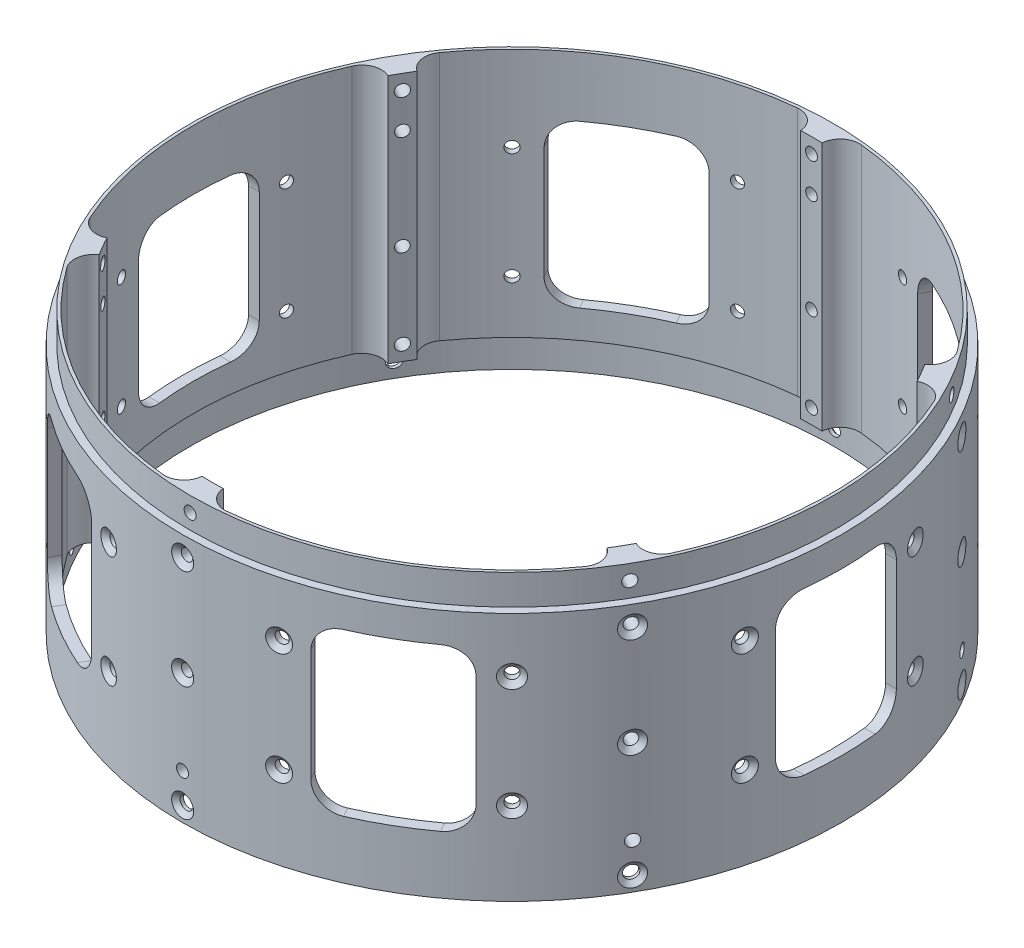
SolidWorks part; units mm, degrees
material "6061-T6 (SS)"
ref_plane "Front Plane" through (0, 0, 0) normal (0, 0, 1) x (1, 0, 0)
ref_plane "Top Plane" through (0, 0, 0) normal (0, 1, 0) x (1, 0, 0)
ref_plane "Right Plane" through (0, 0, 0) normal (1, 0, 0) x (0, 0, -1)
sketch "Sketch1" plane through (0, 0, 0) normal (0, 0, 1) x (1, 0, 0)
  line L0 (0, 42.3951) -> (0, -32.8937) construction
  line L1 (0, -35.6235) -> (0, 35.6235) construction
  line L2 (76.2, -63.5) -> (76.2, 0)
  line L3 (76.2, 0) -> (81.8896, 0)
  line L4 (81.8896, 0) -> (81.8896, -7.6708)
  line L5 (81.8896, -7.6708) -> (83.82, -7.6708)
  line L6 (83.82, -7.6708) -> (83.82, -71.12)
  line L7 (83.82, -71.12) -> (81.9404, -71.12)
  line L8 (81.9404, -71.12) -> (81.9404, -63.5)
  line L9 (81.9404, -63.5) -> (76.2, -63.5)
  line L10 (81.8896, -7.62) -> (84.2911, -7.62) construction
  dimension "D5" = 5.6896
  dimension "D10" = 76.2
  dimension "D2" = 7.62
  dimension "D4" = 7.62
  dimension "D6" = 7.62
revolve "Revolve1" add sketch "Sketch1" angle 360 about L0
sketch "Sketch2" plane through (0, 0, 0) normal (0, 1, 0) x (1, 0, 0)
  line L0 (0, 0) -> (0, 112.6688) construction
  line L1 (0, -35.6235) -> (0, 35.6235) construction
  line L2 (0, 0) -> (-128.6689, 74.287) construction
  line L3 (0, 0) -> (-50.2561, 87.0461) construction
  line L4 (0, 0) -> (-7.6343, 75.8166) construction
  arc A0 (-7.6343, 75.8166) -> (-61.8419, 44.5198) centre (0, 0) ccw construction
  arc A1 (-8.128, 80.7194) -> (-65.841, 47.3988) centre (0, 0) ccw
  arc A2 (-7.1406, 70.9138) -> (-57.8428, 41.6409) centre (0, 0) ccw
  arc A3 (-7.1406, 70.9138) -> (-8.128, 80.7194) centre (-7.6343, 75.8166) ccw
  arc A4 (-65.841, 47.3988) -> (-57.8428, 41.6409) centre (-61.8419, 44.5198) ccw
  circle A5 centre (0, 0) radius 81.8896 construction
  circle A7 centre (0, 0) radius 76.2 construction
  point P5 (-38.1, 65.9911)
  dimension "D2" = 0.762
  dimension "D1" = 60
  dimension "D3" = 30
  dimension "D4" = 5.75
extrude "Cut-Extrude1" cut sketch "Sketch2" against normal through all
pattern_circular "CirPattern1" count 6 over 360 about axis through (0, 42.3951, 0) along (0, 1, 0) of "Cut-Extrude1"
ref_plane "Plane1" through (0, 0, 83.82) normal (0, 0, 1) x (1, 0, 0)
hole_wizard "Tapped Hole for #4-40 Helicoil1" positions "Sketch3" profile "Sketch4" tap size "#4-40" standard "Helicoil® Inch"
sketch "Sketch3" plane through (0, 0, 83.82) normal (0, 0, 1) x (1, 0, 0)
  line L0 (81.8896, 0) -> (-81.8896, 0) construction
  line L1 (2.7181, 0) -> (-2.7181, 0) construction
  line L2 (2.7181, 0) -> (-2.7181, 0) construction
  line L3 (0, 0) -> (0, -3.81) construction
  line L5 (-2.7181, -63.5) -> (2.7181, -63.5) construction
  line L6 (-2.7181, -63.5) -> (2.7181, -63.5) construction
  line L7 (0, -63.5) -> (0, -59.69) construction
  point P0 (0, -3.81)
  point P20 (0, -59.69)
  point P41 (0, 0)
  point P42 (0, 0)
  dimension "D1" = 3.81
  dimension "D2" = 3.81
cosmetic thread "Hole Thread1" parameters "D1"=3.556, "D2"=3.7414
cosmetic thread "Hole Thread6" parameters "D1"=3.556, "D2"=3.7414
sketch "Sketch4" plane through (0, -3.81, 83.82) normal (1, 0, 0) x (0, -1, 0)
  line L0 (0, 0) -> (0, 26.3157)
  line L1 (0, 26.3157) -> (1.524, 25.4)
  line L2 (1.524, 25.4) -> (1.524, 0)
  line L5 (1.524, 0) -> (0, 0)
  line L10 (0, 26.3157) -> (-1.524, 25.4) construction
  line L11 (0, -6.35) -> (0, 107.95) construction
  dimension "Tap Drill Dia." = 3.048
  dimension "Tap Drill Depth" = 25.4
  dimension "Drill Angle" = 118
hole_wizard "CSK for #4 Flat Head Machine Screw (100)1" positions "Sketch5" profile "Sketch6" countersink size "#4" standard "ANSI Inch"
sketch "Sketch5" plane through (0, 0, 83.82) normal (0, 0, 1) x (1, 0, 0)
  line L0 (-2.7181, -63.5) -> (2.7181, -63.5) construction
  line L1 (-2.7181, -63.5) -> (2.7181, -63.5) construction
  line L2 (0, -63.5) -> (0, -67.31) construction
  point P0 (0, -67.31)
  dimension "D1" = 3.81
sketch "Sketch6" plane through (0, -67.31, 83.82) normal (1, 0, 0) x (0, -1, 0)
  line L0 (0, 0) -> (0, 26.3806)
  line L1 (0, 26.3806) -> (1.6319, 25.4)
  line L2 (1.6319, 25.4) -> (1.6319, 1.0284)
  line L3 (1.6319, 1.0284) -> (2.8575, 0)
  line L5 (2.8575, 0) -> (0, 0)
  line L6 (-1.6319, 1.0284) -> (-2.8575, 0) construction
  line L10 (0, 26.3806) -> (-1.632, 25.4) construction
  line L11 (0, -6.35) -> (0, 107.95) construction
  dimension "Hole Dia." = 3.2639
  dimension "Hole Depth" = 25.4
  dimension "Near C'Sink Dia." = 5.715
  dimension "Near C'Sink Angle" = 100
  dimension "Drill Angle" = 118
hole_wizard "CSK for #4 Flat Head Machine Screw (100)3" positions "Sketch12" profile "Sketch13" countersink size "#4" standard "ANSI Inch"
sketch "Sketch12" plane through (0, 0, 83.82) normal (0, 0, 1) x (1, 0, 0)
  line L0 (-2.7181, -63.5) -> (2.7181, -63.5) construction
  point P0 (0, -38.1)
  point P2 (0, -12.7)
  point P6 (0, -63.5)
  dimension "D1" = 25.4
  dimension "D2" = 50.8
sketch "Sketch13" plane through (0, -38.1, 83.82) normal (1, 0, 0) x (0, -1, 0)
  line L0 (0, 0) -> (0, 26.2852)
  line L1 (0, 26.2852) -> (1.4732, 25.4)
  line L2 (1.4732, 25.4) -> (1.4732, 1.1616)
  line L3 (1.4732, 1.1616) -> (2.8575, 0)
  line L5 (2.8575, 0) -> (0, 0)
  line L6 (-1.4732, 1.1616) -> (-2.8575, 0) construction
  line L10 (0, 26.2852) -> (-1.4732, 25.4) construction
  line L11 (0, -6.35) -> (0, 107.95) construction
  dimension "Hole Dia." = 2.9464
  dimension "Hole Depth" = 25.4
  dimension "Near C'Sink Dia." = 5.715
  dimension "Near C'Sink Angle" = 100
  dimension "Drill Angle" = 118
pattern_circular "CirPattern2" count 6 over 360 about axis through (0, 42.3951, 0) along (0, 1, 0) of "Tapped Hole for #4-40 Helicoil1", "CSK for #4 Flat Head Machine Screw (100)1", "CSK for #4 Flat Head Machine Screw (100)3"
sketch "Sketch7" plane through (0, 0, 0) normal (1, 0, 0) x (0, 0, -1)
  line L1 (-9.017, -15.24) -> (9.017, -15.24)
  line L2 (-15.367, -21.59) -> (-15.367, -50.038)
  line L3 (-9.017, -56.388) -> (9.017, -56.388)
  line L4 (15.367, -21.59) -> (15.367, -50.038)
  line L5 (-15.367, -15.24) -> (15.367, -56.388) construction
  line L6 (-15.367, -56.388) -> (15.367, -15.24) construction
  arc A0 (-15.367, -50.038) -> (-9.017, -56.388) centre (-9.017, -50.038) ccw
  arc A1 (9.017, -56.388) -> (15.367, -50.038) centre (9.017, -50.038) ccw
  arc A2 (15.367, -21.59) -> (9.017, -15.24) centre (9.017, -21.59) ccw
  arc A3 (-9.017, -15.24) -> (-15.367, -21.59) centre (-9.017, -21.59) ccw
  point P0 (0, -35.814)
  dimension "D4" = 6.35
  dimension "D1" = 41.148
  dimension "D2" = 30.734
  dimension "D3" = 15.24
extrude "Cut-Extrude2" cut sketch "Sketch7" against normal through all
sketch "Sketch9" plane through (0, -7.6708, 0) normal (0, 1, 0) x (1, 0, 0)
  line L0 (-49.5, 0) -> (-83.82, 0)
  line L1 (-50.2347, -13.4603) -> (-80.9639, -21.6942)
  line L2 (-83.82, 11.0351) -> (-83.82, -11.0351) construction
  line L3 (-83.82, -11.0351) -> (-78.1078, -32.3533) construction
  arc A0 (-83.3336, 9.017) -> (-83.3336, -9.017) centre (0, 0) ccw construction
  circle A1 centre (0, 0) radius 83.82 construction
  dimension "D1" = 15
ref_plane "Plane3" through (-80.9639, -7.6708, 21.6942) normal (-0.9659, 0, 0.2588) x (0.2588, 0, 0.9659)
hole_wizard "CSK for #4 Flat Head Machine Screw (100)2" positions "Sketch10" profile "Sketch11" countersink size "#4" standard "ANSI Inch"
sketch "Sketch10" plane through (-80.9639, -7.6708, 21.6942) normal (-0.9659, 0, 0.2588) x (0.2588, 0, 0.9659)
  line L0 (0, 0) -> (0, -13.9192) construction
  line L1 (0, -13.9192) -> (0, -42.3672) construction
  line L3 (0, -13.9192) -> (-6.4831, -13.9192) construction
  line L5 (0, -28.1432) -> (-6.4831, -28.1432) construction
  line L8 (-6.4831, -13.9192) -> (-6.4831, -42.3672) construction
  point P0 (0, -13.9192)
  point P2 (0, -42.3672)
  point P19 (0, 0)
  point P23 (0, 0)
sketch "Sketch11" plane through (-80.9639, -21.59, 21.6942) normal (0, 1, 0) x (0.2588, 0, 0.9659)
  line L0 (0, 0) -> (0, 26.2852)
  line L1 (0, 26.2852) -> (1.4732, 25.4)
  line L2 (1.4732, 25.4) -> (1.4732, 1.1616)
  line L3 (1.4732, 1.1616) -> (2.8575, 0)
  line L5 (2.8575, 0) -> (0, 0)
  line L6 (-1.4732, 1.1616) -> (-2.8575, 0) construction
  line L10 (0, 26.2852) -> (-1.4732, 25.4) construction
  line L11 (0, -6.35) -> (0, 107.95) construction
  dimension "Hole Dia." = 2.9464
  dimension "Hole Depth" = 25.4
  dimension "Near C'Sink Dia." = 5.715
  dimension "Near C'Sink Angle" = 100
  dimension "Drill Angle" = 118
mirror "Mirror1" about plane through (0, 0, 0) normal (0, 0, 1) of "CSK for #4 Flat Head Machine Screw (100)2"
pattern_circular "CirPattern5" count 6 over 360 about axis through (0, -7.6708, 0) along (0, 1, 0) of "Cut-Extrude2", "Mirror1"
ref_plane "Plane2" [suppressed] through (0, 0, 0) normal (-0.7071, 0, 0.7071) x (0.7071, 0, 0.7071)
sketch "Sketch8" [suppressed] plane through (0, 0, 0) normal (-0.7071, 0, 0.7071) x (0.7071, 0, 0.7071)
  line L0 (0, 0) -> (89.1919, 0) construction
  line L1 (-9.017, -17.145) -> (-6.858, -17.145)
  line L2 (-12.192, -20.32) -> (-12.192, -31.115)
  line L3 (-9.017, -34.29) -> (-6.858, -34.29)
  line L4 (-3.683, -20.32) -> (-3.683, -31.115)
  line L5 (0, 0) -> (0, -89.2767) construction
  line L6 (-83.82, -71.12) -> (83.82, -71.12) construction
  line L7 (-7.9375, -52.07) -> (-4.7625, -52.07)
  line L8 (-9.525, -53.6575) -> (-9.525, -56.8325)
  line L9 (-7.9375, -58.42) -> (-4.7625, -58.42)
  line L10 (-3.175, -53.6575) -> (-3.175, -56.8325)
  arc A0 (-9.017, -34.29) -> (-12.192, -31.115) centre (-9.017, -31.115) cw
  arc A1 (-3.683, -31.115) -> (-6.858, -34.29) centre (-6.858, -31.115) cw
  arc A2 (-3.683, -20.32) -> (-6.858, -17.145) centre (-6.858, -20.32) ccw
  arc A3 (-9.017, -17.145) -> (-12.192, -20.32) centre (-9.017, -20.32) ccw
  arc A4 (-9.525, -56.8325) -> (-7.9375, -58.42) centre (-7.9375, -56.8325) ccw
  arc A5 (-3.175, -56.8325) -> (-4.7625, -58.42) centre (-4.7625, -56.8325) cw
  arc A6 (-3.175, -53.6575) -> (-4.7625, -52.07) centre (-4.7625, -53.6575) ccw
  arc A7 (-7.9375, -52.07) -> (-9.525, -53.6575) centre (-7.9375, -53.6575) ccw
  circle A8 centre (-6.35, -48.895) radius 1.5875
  circle A9 centre (-6.35, -61.595) radius 1.5875
  point P20 (-3.175, -55.245)
  point P29 (-6.35, -58.42)
  dimension "D1" = 3.175
  dimension "D8" = 1.5875
  dimension "D11" = 3.175
  dimension "D12" = 3.175
  dimension "D2" = 8.509
  dimension "D3" = 17.145
  dimension "D4" = 17.145
  dimension "D5" = 3.683
  dimension "D6" = 6.35
  dimension "D7" = 6.35
  dimension "D9" = 6.35
  dimension "D10" = 12.7
  dimension "D13" = 3.175
  dimension "D14" = 3.175
extrude "Cut-Extrude3" [suppressed] cut sketch "Sketch8" along normal through all
equation "\"nominalLength\"=2.5"
equation "\"D8@Sketch1\"=\"nominalLength\""
equation "\"D12@Sketch8\"=\"D11@Sketch8\""
